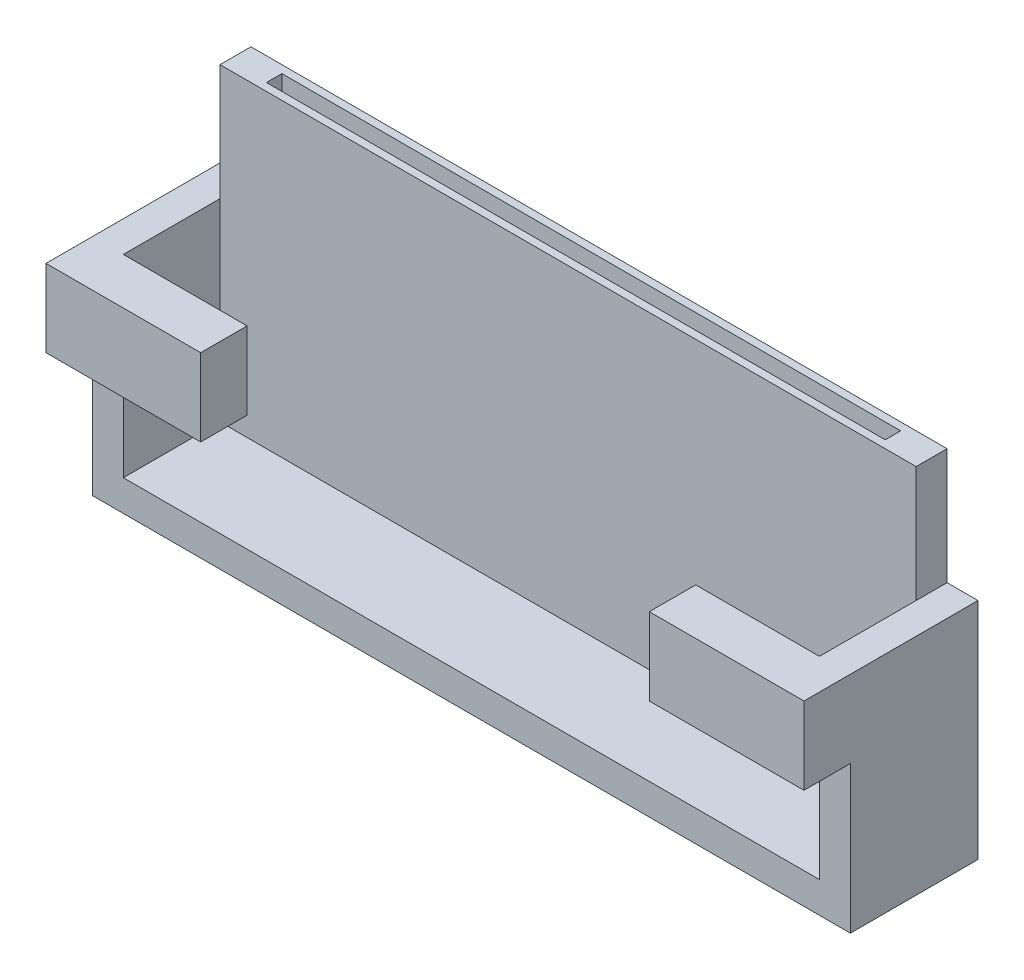
SolidWorks part; units mm, degrees
ref_plane "Front Plane" through (0, 0, 0) normal (0, 0, 1) x (1, 0, 0)
ref_plane "Top Plane" through (0, 0, 0) normal (0, 1, 0) x (1, 0, 0)
ref_plane "Right Plane" through (0, 0, 0) normal (1, 0, 0) x (0, 0, -1)
sketch "Sketch1" plane through (0, 0, 0) normal (0, 0, 1) x (1, 0, 0)
  line L0 (-24.5, 2.5) -> (24.5, 2.5)
  line L1 (-22.5, 10) -> (22.5, 10)
  line L2 (-22.5, 10) -> (-22.5, -10)
  line L3 (-22.5, -10) -> (22.5, -10)
  line L4 (22.5, 10) -> (22.5, -10)
  line L5 (-22.5, 10) -> (22.5, -10) construction
  line L6 (-22.5, -10) -> (22.5, 10) construction
  line L7 (-24.5, 12) -> (24.5, 12)
  line L8 (-24.5, 12) -> (-24.5, -12)
  line L9 (-24.5, -12) -> (24.5, -12)
  line L10 (24.5, 12) -> (24.5, -12)
  line L11 (-24.5, 12) -> (24.5, -12) construction
  line L12 (-24.5, -12) -> (24.5, 12) construction
  point P0 (0, 0)
  point P6 (0, 0)
  dimension "D1" = 45
  dimension "D2" = 20
  dimension "D3" = 49
  dimension "D4" = 24
  dimension "D5" = 14.5
extrude "Boss-Extrude1" add sketch "Sketch1" along normal blind 2 contours L4 L1 L2 L0 | L4 L0 L2 L3 region at (0, 6.25, 0) region at (0, -3.75, 0)
extrude "Boss-Extrude2" add sketch "Sketch1<3>" along normal blind 8.25 contours L10 L0 L4 L3 L2 L8 L9 region at (-23.5, 1.989, 0)
sketch "Sketch1<3>" plane through (0, 0, 0) normal (0, 0, 1) x (1, 0, 0) same geometry as "Sketch1"
sketch "Sketch3" plane through (0, 0, 8.25) normal (0, 0, 1) x (1, 0, 0)
  line L0 (0, 10) -> (0, -12) construction
  line L1 (-24.5, 2.5) -> (-14.5, 2.5)
  line L2 (-24.5, 2.5) -> (-24.5, -2.5)
  line L3 (-24.5, -2.5) -> (-14.5, -2.5)
  line L4 (-14.5, 2.5) -> (-14.5, -2.5)
  line L6 (-24.5, -12) -> (24.5, -12) construction
  line L11 (-24.5, 2.5) -> (-24.5, -12) construction
  line L12 (24.5, 2.5) -> (24.5, -2.5)
  line L13 (24.5, -2.5) -> (14.5, -2.5)
  line L14 (14.5, 2.5) -> (14.5, -2.5)
  line L15 (24.5, 2.5) -> (14.5, 2.5)
  point P17 (-24.5, -4.75)
  dimension "D1" = 5
  dimension "D2" = 10
  dimension "D3" = 0
  dimension "D4" = 9.5
extrude "Boss-Extrude3" add sketch "Sketch3" along normal blind 3
sketch "Sketch4" plane through (0, 10, 0) normal (0, 1, 0) x (1, 0, 0)
  line L0 (-22.5, -2) -> (-22.5, 0) construction
  line L1 (-20, -0.5) -> (20, -0.5)
  line L2 (-20, -0.5) -> (-20, -1.5)
  line L3 (-20, -1.5) -> (20, -1.5)
  line L4 (20, -0.5) -> (20, -1.5)
  line L5 (-22.5, 0) -> (22.5, 0) construction
  point P8 (-22.5, -1)
  dimension "D1" = 40
  dimension "D2" = 1
  dimension "D3" = 2.5
  dimension "D4" = 0.5
extrude "Cut-Extrude1" cut sketch "Sketch4" against normal blind 2
sketch "Sketch6" plane through (0, 0, 0) normal (0, 0, -1) x (-1, 0, 0)
  line L2 (-7.5, 1.5) -> (7.5, 1.5)
  line L3 (-7.5, 1.5) -> (-7.5, -1.5)
  line L4 (-7.5, -1.5) -> (7.5, -1.5)
  line L5 (7.5, 1.5) -> (7.5, -1.5)
  line L6 (-7.5, 1.5) -> (7.5, -1.5) construction
  line L7 (-7.5, -1.5) -> (7.5, 1.5) construction
  point P0 (0, 0)
  dimension "D1" = 15
  dimension "D2" = 3
ref_plane "Plane5" through (0, 0, -5) normal (0, 0, 1) x (1, 0, 0)
sketch "Sketch7" plane through (0, 0, -5) normal (0, 0, 1) x (1, 0, 0)
  line L1 (-7.5, 2.5) -> (7.5, 2.5)
  line L2 (-7.5, 2.5) -> (-7.5, -2.5)
  line L3 (-7.5, -2.5) -> (7.5, -2.5)
  line L4 (7.5, 2.5) -> (7.5, -2.5)
  line L5 (-7.5, 2.5) -> (7.5, -2.5) construction
  line L6 (-7.5, -2.5) -> (7.5, 2.5) construction
  point P0 (0, 0)
  dimension "D1" = 5
  dimension "D2" = 15
loft "Loft2" add profiles "Sketch6", "Sketch7" start constraint normal to profile start tangent length 1 connector at (-7.5, 1.5, 0) connector at (-7.5, 2.5, -5)
equation "\"D3@Sketch1\"=\"D1@Sketch1\"+4"
equation "\"D4@Sketch1\"=\"D2@Sketch1\"+4"
